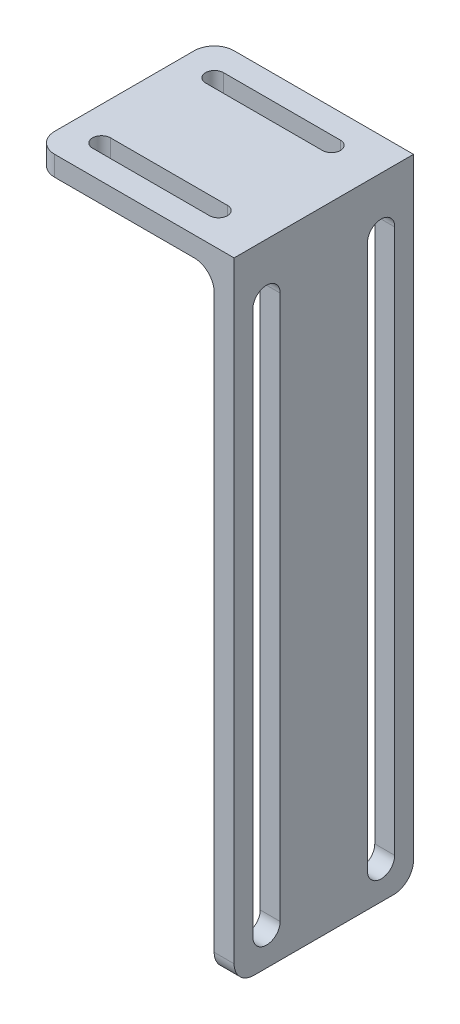
SolidWorks part; units mm, degrees
material "ABS"
ref_plane "Front Plane" through (0, 0, 0) normal (0, 0, 1) x (1, 0, 0)
ref_plane "Top Plane" through (0, 0, 0) normal (0, 1, 0) x (1, 0, 0)
ref_plane "Right Plane" through (0, 0, 0) normal (1, 0, 0) x (0, 0, -1)
sketch "Sketch1" plane through (0, 0, 0) normal (0, 0, 1) x (1, 0, 0)
  line L0 (0, 0) -> (3, 0)
  line L1 (3, 0) -> (3, 95)
  line L2 (3, 95) -> (-27, 95)
  line L3 (-27, 95) -> (-27, 92)
  line L4 (-27, 92) -> (0, 92)
  line L5 (0, 92) -> (0, 0)
  dimension "D1" = 27
  dimension "D2" = 95
  dimension "D3" = 3
  dimension "D4" = 3
extrude "Boss-Extrude1" add sketch "Sketch1" along normal blind 27
sketch "Sketch6" plane through (3, 0, 0) normal (1, 0, 0) x (0, 0, -1)
  line L0 (-22.12, 95) -> (-22.12, 0) construction
  line L1 (-27, 95) -> (0, 95) construction
  line L3 (-22.12, 86.95) -> (-22.12, 5.05) construction
  line L4 (-20.07, 86.95) -> (-20.07, 5.05)
  line L5 (-24.17, 86.95) -> (-24.17, 5.05)
  line L6 (-27, 0) -> (0, 0) construction
  line L7 (-4.88, 95) -> (-4.88, 0) construction
  line L8 (-27, 0) -> (-27, 95) construction
  line L9 (0, 0) -> (0, 95) construction
  line L10 (-4.88, 86.95) -> (-4.88, 5.05) construction
  line L11 (-2.83, 86.95) -> (-2.83, 5.05)
  line L12 (-6.93, 86.95) -> (-6.93, 5.05)
  arc A0 (-20.07, 86.95) -> (-24.17, 86.95) centre (-22.12, 86.95) ccw
  arc A1 (-24.17, 5.05) -> (-20.07, 5.05) centre (-22.12, 5.05) ccw
  arc A2 (-2.83, 86.95) -> (-6.93, 86.95) centre (-4.88, 86.95) ccw
  arc A3 (-6.93, 5.05) -> (-2.83, 5.05) centre (-4.88, 5.05) ccw
  point P8 (-22.12, 46)
  point P13 (-22.12, 89)
  point P23 (-4.88, 46)
  point P28 (-4.88, 89)
  dimension "D7" = 6
  dimension "D1" = 4.1
  dimension "D2" = 6
  dimension "D3" = 4.88
  dimension "D5" = 4.88
  dimension "D6" = 4.1
extrude "Cut-Extrude1" cut sketch "Sketch6" against normal through all
sketch "Sketch7" plane through (0, 95, 0) normal (0, 1, 0) x (1, 0, 0)
  line L0 (-27, -5) -> (3, -5) construction
  line L1 (-27, -13.5) -> (3, -13.5) construction
  line L2 (3, -27) -> (3, 0) construction
  line L3 (-21.95, -5) -> (-4.35, -5) construction
  line L4 (-21.95, -3.65) -> (-4.35, -3.65)
  line L5 (-21.95, -6.35) -> (-4.35, -6.35)
  line L6 (-27, -27) -> (-27, 0) construction
  line L7 (-27, -22) -> (3, -22) construction
  line L8 (3, 0) -> (-27, 0) construction
  line L9 (-21.95, -22) -> (-4.35, -22) construction
  line L10 (-21.95, -20.65) -> (-4.35, -20.65)
  line L11 (-21.95, -23.35) -> (-4.35, -23.35)
  line L12 (3, -27) -> (-27, -27) construction
  arc A0 (-21.95, -3.65) -> (-21.95, -6.35) centre (-21.95, -5) ccw
  arc A1 (-4.35, -6.35) -> (-4.35, -3.65) centre (-4.35, -5) ccw
  arc A2 (-21.95, -20.65) -> (-21.95, -23.35) centre (-21.95, -22) ccw
  arc A3 (-4.35, -23.35) -> (-4.35, -20.65) centre (-4.35, -22) ccw
  point P8 (-13.15, -5)
  point P13 (-23.3, -5)
  point P14 (-3, -5)
  point P21 (-13.15, -22)
  point P28 (-3, -22)
  dimension "D2" = 6
  dimension "D1" = 5
  dimension "D3" = 2.7
  dimension "D4" = 20.3
  dimension "D5" = 2.7
  dimension "D6" = 5
  dimension "D7" = 6
  dimension "D8" = 8.5
extrude "Cut-Extrude2" cut sketch "Sketch7" against normal through all contours L4 A1 L5 A0 | L11 A3 L10 A2
fillet "Fillet1" radius 3 1 edges at (0, 92, 13.5)
fillet "Fillet2" radius 3 4 edges at (1.5, 0, 0) (1.5, 0, 27) (-27, 93.5, 27) (-27, 93.5, 0)
sketch "Sketch8" plane through (0, 95, 0) normal (0, 1, 0) x (1, 0, 0)
  line L0 (-27, -13.5) -> (3, -13.5) construction
  line L1 (-27, -24) -> (-27, -3) construction
  line L2 (3, -27) -> (3, 0) construction
sketch "Sketch9" plane through (3, 0, 0) normal (1, 0, 0) x (0, 0, -1)
  line L0 (-13.5, 95) -> (-13.5, 0) construction
  line L1 (-27, 95) -> (0, 95) construction
  line L2 (-24, 0) -> (-3, 0) construction
